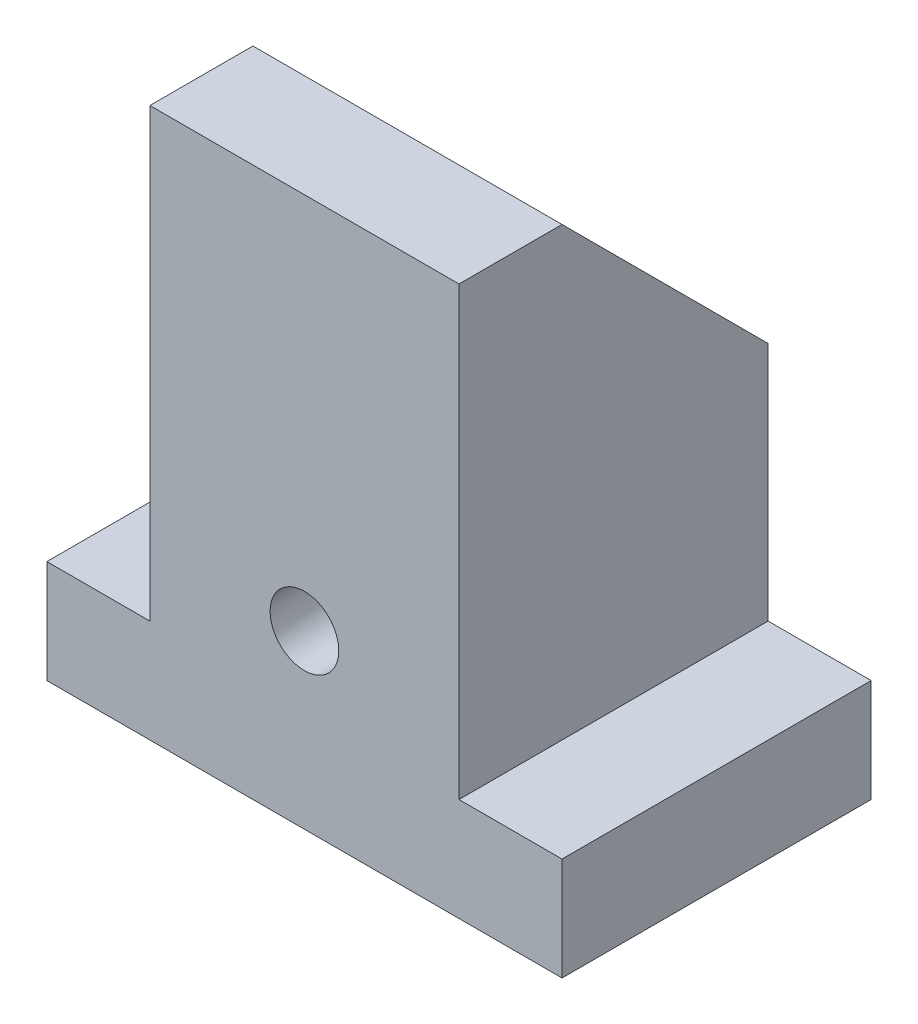
SolidWorks part; units mm, degrees
ref_plane "Ebene vorne" through (0, 0, 0) normal (0, 0, 1) x (1, 0, 0)
ref_plane "Ebene oben" through (0, 0, 0) normal (0, 1, 0) x (1, 0, 0)
ref_plane "Ebene rechts" through (0, 0, 0) normal (1, 0, 0) x (0, 0, -1)
sketch "Sketch1" plane through (0, 0, 0) normal (0, 1, 0) x (1, 0, 0)
  line L1 (0, 0) -> (9, 0)
  line L2 (0, 0) -> (0, 9)
  line L3 (0, 9) -> (9, 9)
  line L4 (9, 0) -> (9, 9)
  dimension "D1" = 9
  dimension "D2" = 9
extrude "Boss-Extrude1" add sketch "Sketch1" along normal blind 16
fillet "Chamfer1" radius 6 1 edges at (4.5, 16, -9) profile chamfer
sketch "Sketch2" plane through (0, 0, 0) normal (0, -1, 0) x (1, 0, 0)
  line L0 (9, -4.5) -> (0, -4.5) construction
  line L1 (9, 0) -> (9, -9) construction
  line L2 (0, -9) -> (0, 0) construction
  circle A0 centre (4.5, -4.5) radius 3.1
  dimension "D1" = 6.2
extrude "Cut-Extrude1" cut sketch "Sketch2" against normal blind 8
sketch "Sketch3" plane through (0, 0, -9) normal (0, 0, -1) x (-1, 0, 0)
  line L0 (-4.5, 0) -> (-4.5, 10) construction
  line L1 (-9, 0) -> (0, 0) construction
  line L2 (0, 10) -> (-9, 10) construction
  line L3 (-7.6, 8) -> (-1.4, 8) construction
  line L4 (-7.6, 8) -> (-1.4, 8) construction
  circle A0 centre (-4.5, 5) radius 1
  dimension "D1" = 2
  dimension "D2" = 3
extrude "Cut-Extrude2" cut sketch "Sketch3" against normal up to surface (9 mm away) up to face at (4.5, 8, 0)
sketch "Sketch4" plane through (0, 0, 0) normal (0, -1, 0) x (-1, 0, 0)
  line L0 (-4.5, 9) -> (-4.5, 0) construction
  line L11 (-9, 0) -> (-12, 0)
  line L12 (-9, 0) -> (-9, 9)
  line L13 (-9, 9) -> (-12, 9)
  line L14 (-12, 0) -> (-12, 9)
  line L15 (-9, 9) -> (0, 9) construction
  line L16 (0, 0) -> (-9, 0) construction
  line L17 (3, 0) -> (3, 9)
  line L18 (0, 9) -> (3, 9)
  line L19 (0, 0) -> (0, 9)
  line L20 (0, 0) -> (3, 0)
  dimension "D1" = 15
extrude "Boss-Extrude2" add sketch "Sketch4" against normal blind 3
